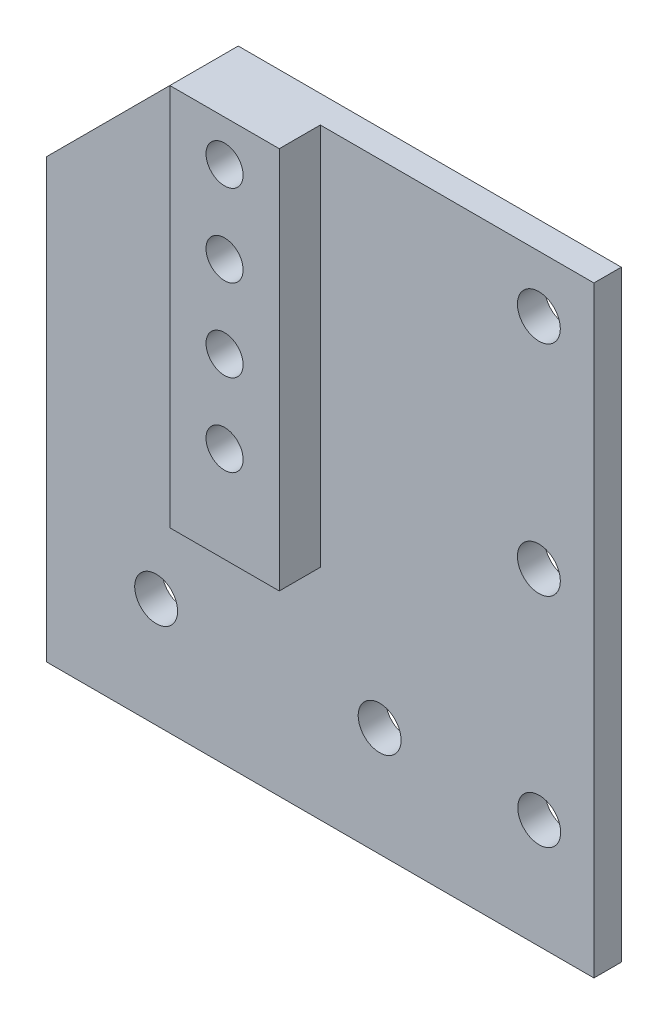
SolidWorks part; units mm, degrees
ref_plane "Front Plane" through (0, 0, 0) normal (0, 0, 1) x (1, 0, 0)
ref_plane "Top Plane" through (0, 0, 0) normal (0, 1, 0) x (1, 0, 0)
ref_plane "Right Plane" through (0, 0, 0) normal (1, 0, 0) x (0, 0, -1)
sketch "Sketch1" plane through (0, 0, 0) normal (0, 0, 1) x (1, 0, 0)
  line L15 (-266.7, -12.7) -> (-266.7, 57.15)
  line L16 (-266.7, 609.6) -> (-266.7, -16.7024) construction
  line L18 (-279.4, -12.7) -> (-266.7, -12.7)
  line L19 (-279.4, -12.7) -> (-330.2, -12.7)
  line L20 (-330.2, -12.7) -> (-330.2, 12.7)
  line L21 (-330.2, 12.7) -> (-330.2, 38.1)
  line L22 (-311.15, 57.15) -> (-330.2, 38.1)
  line L23 (-279.4, 57.15) -> (-311.15, 57.15)
  line L24 (-266.7, 57.15) -> (-279.4, 57.15)
  dimension "D1" = 69.85
extrude "Boss-Extrude1" add sketch "Sketch1" along normal blind 3.175
sketch "Sketch2" plane through (0, 0, 3.175) normal (0, 0, 1) x (1, 0, 0)
  line L10 (-273.05, 25.4) -> (-273.0882, 50.7989) construction
  line L11 (-273.05, 0) -> (-273.05, 25.4) construction
  line L12 (-273.05, -12.7) -> (-273.05, 0) construction
  line L13 (-279.4, -12.7) -> (-266.7, -12.7) construction
  line L14 (-330.2, 0) -> (-317.5, 0) construction
  line L15 (-317.5, 0) -> (-292.1, 0) construction
  line L16 (-330.2, -12.7) -> (-330.2, 12.7) construction
hole_wizard "#10 Clearance Hole1" positions "Sketch3" profile "Sketch4" hole size "#10" standard "ANSI Inch" end condition through all
sketch "Sketch3" plane through (0, 0, 3.175) normal (0, 0, 1) x (1, 0, 0)
  point P30 (-273.0882, 50.5983)
  point P33 (-273.0882, 25.2365)
  point P36 (-273.05, 0)
  point P39 (-291.5645, 0)
  point P41 (-317.5, 0)
sketch "Sketch4" plane through (-273.0882, 50.5983, 3.175) normal (1, 0, 0) x (0, -1, 0)
  line L0 (0, 0) -> (0, 3.175)
  line L1 (0, 3.175) -> (2.4892, 3.175)
  line L2 (2.4892, 3.175) -> (2.4892, 0)
  line L5 (2.4892, 0) -> (0, 0)
  line L11 (0, -6.35) -> (0, 107.95) construction
  dimension "Thru Hole Dia." = 4.9784
  dimension "Thru Hole Depth" = 3.175
sketch "Sketch5" plane through (0, 0, 3.175) normal (0, 0, 1) x (1, 0, 0)
  line L0 (-311.15, 12.7) -> (-298.45, 12.7)
  line L9 (-311.15, 57.15) -> (-311.15, 12.7)
  line L10 (-298.45, 12.7) -> (-298.45, 57.15)
  line L13 (-266.7, 57.15) -> (-311.15, 57.15) construction
  line L17 (-298.45, 57.15) -> (-311.15, 57.15)
  dimension "D1" = 44.45
  dimension "D2" = 12.7
extrude "Boss-Extrude2" add sketch "Sketch5" along normal blind 4.7625
sketch "Sketch6" plane through (0, 0, 7.9375) normal (0, 0, 1) x (1, 0, 0)
  line L0 (-304.8, 57.15) -> (-304.8, 52.3875) construction
  line L1 (-304.8, 52.3875) -> (-304.8, 42.8625) construction
  line L2 (-304.8, 42.8625) -> (-304.8, 33.3375) construction
  line L4 (-304.8, 33.3375) -> (-304.8, 23.8125) construction
  line L5 (-298.45, 57.15) -> (-311.15, 57.15) construction
  point P2 (-304.8, 57.15)
  dimension "D1" = 9.525
  dimension "D2" = 4.7625
  dimension "D3" = 9.525
  dimension "D4" = 9.525
hole_wizard "#8 Clearance Hole1" positions "Sketch7" profile "Sketch8" hole size "#8" standard "ANSI Inch" end condition through all
sketch "Sketch7" plane through (0, 0, 7.9375) normal (0, 0, 1) x (1, 0, 0)
  point P0 (-304.8, 42.8625)
  point P3 (-304.8, 52.3875)
  point P7 (-304.8, 33.3375)
  point P10 (-304.8, 23.8125)
sketch "Sketch8" plane through (-304.8, 42.8625, 7.9375) normal (1, 0, 0) x (0, -1, 0)
  line L0 (0, 0) -> (0, 7.9375)
  line L1 (0, 7.9375) -> (2.1526, 7.9375)
  line L2 (2.1526, 7.9375) -> (2.1526, 0)
  line L5 (2.1526, 0) -> (0, 0)
  line L11 (0, -6.35) -> (0, 107.95) construction
  dimension "Thru Hole Dia." = 4.3053
  dimension "Thru Hole Depth" = 7.9375
